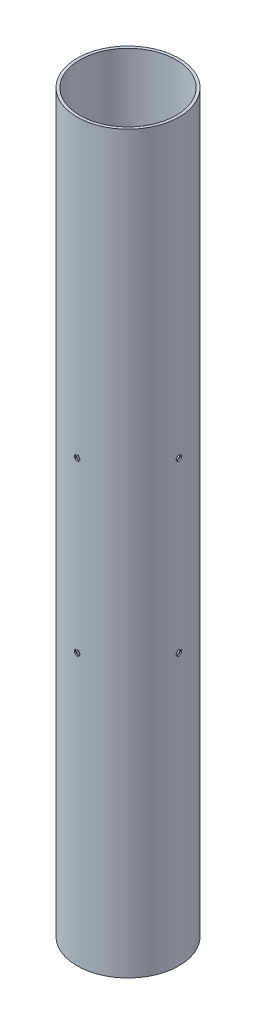
SolidWorks part; units mm, degrees
material "Hexcel AS4C (3000 Filaments)"
ref_plane "Front Plane" through (0, 0, 0) normal (0, 0, 1) x (1, 0, 0)
ref_plane "Top Plane" through (0, 0, 0) normal (0, 1, 0) x (1, 0, 0)
ref_plane "Right Plane" through (0, 0, 0) normal (1, 0, 0) x (0, 0, -1)
sketch "Sketch1" plane through (0, 0, 0) normal (0, 1, 0) x (1, 0, 0)
  circle A0 centre (0, 0) radius 50.8
  dimension "D1" = 101.6
extrude "Tube Extrusion" add sketch "Sketch1" along normal blind 774.7 thin thin type one direction wall 2.921
ref_plane "Hole Plane" through (0, 0, 53.721) normal (0, 0, 1) x (1, 0, 0)
sketch "Sketch3" plane through (0, 0, 53.721) normal (0, 0, 1) x (1, 0, 0)
  line L0 (0, 774.7) -> (0, 0) construction
  line L1 (50.8, 774.7) -> (-50.8, 774.7) construction
  line L2 (53.721, 774.7) -> (-53.721, 774.7) construction
  circle A0 centre (0, 463.55) radius 1.6383
  circle A1 centre (0, 285.75) radius 1.6383
  dimension "D1" = 3.2766
  dimension "D3" = 3.2766
  dimension "D2" = 311.15
  dimension "D4" = 488.95
extrude "Bulkhead Holes" cut sketch "Sketch3" against normal up to next
pattern_circular "Hole Pattern" count 4 over 360 about axis through (0, 774.7, 0) along (0, -1, 0) of "Bulkhead Holes" reverse direction yes
sketch "Sketch4" plane through (0, 0, 53.721) normal (0, 0, 1) x (1, 0, 0)
  circle A0 centre (0, 285.75) radius 1.6383 construction
  circle A1 centre (0, 463.55) radius 1.6383 construction
  circle A3 centre (0, 285.75) radius 1.6383
  circle A4 centre (0, 463.55) radius 1.6383
  circle A7 centre (0, 463.55) radius 2.9083
  circle A8 centre (0, 285.75) radius 2.9083
  dimension "D2" = 1.27
extrude "Cut-Extrude1" cut sketch "Sketch4" against normal blind 1.27
pattern_circular "CirPattern1" count 4 over 360 about axis through (0, 774.7, 0) along (0, -1, 0) of "Cut-Extrude1"
